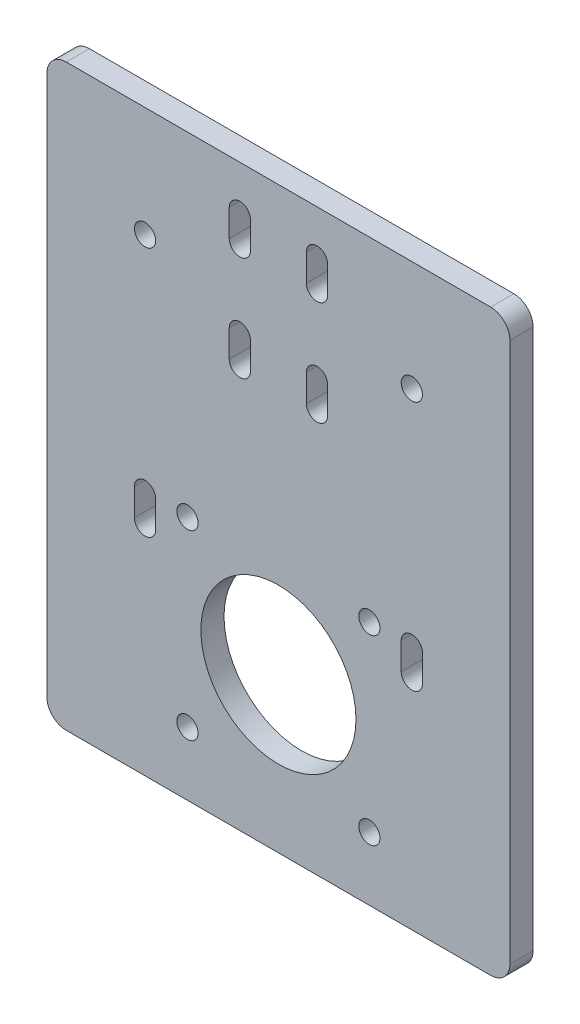
SolidWorks part; units mm, degrees
ref_plane "Front Plane" through (0, 0, 0) normal (0, 0, 1) x (1, 0, 0)
ref_plane "Top Plane" through (0, 0, 0) normal (0, 1, 0) x (1, 0, 0)
ref_plane "Right Plane" through (0, 0, 0) normal (1, 0, 0) x (0, 0, -1)
sketch "Sketch3" plane through (0, 0, 0) normal (0, 0, 1) x (1, 0, 0)
  line L1 (-55, -75) -> (55, -75)
  line L2 (-60, -70) -> (-60, 70)
  line L3 (-55, 75) -> (55, 75)
  line L4 (60, -70) -> (60, 70)
  line L5 (-60, -75) -> (60, 75) construction
  line L6 (-60, 75) -> (60, -75) construction
  arc A0 (-55, -75) -> (-60, -70) centre (-55, -70) cw
  arc A1 (55, -75) -> (60, -70) centre (55, -70) ccw
  arc A2 (55, 75) -> (60, 70) centre (55, 70) cw
  arc A3 (-60, 70) -> (-55, 75) centre (-55, 70) cw
  point P0 (0, 0)
  dimension "D3" = 5
  dimension "D1" = 120
  dimension "D2" = 150
extrude "Boss-Extrude1" add sketch "Sketch3" along normal blind 6
sketch "Sketch4" plane through (0, 0, 6) normal (0, 0, 1) x (1, 0, 0)
  line L0 (-55, -75) -> (55, -75) construction
  circle A0 centre (0, -35) radius 20.1
  dimension "D1" = 40.2
  dimension "D2" = 40
extrude "Cut-Extrude1" cut sketch "Sketch4" against normal blind 39.2
hole_wizard "M5 Clearance Hole1" positions "Sketch5" profile "Sketch6" hole size "M5" standard "ANSI Metric" end condition through all
sketch "Sketch5" plane through (0, 0, 6) normal (0, 0, 1) x (1, 0, 0)
  circle A0 centre (0, -35) radius 20.1 construction
  point P0 (-23.57, -11.43)
  point P2 (23.57, -11.43)
  point P4 (23.57, -58.57)
  point P6 (-23.57, -58.57)
  dimension "D2" = 23.57
  dimension "D3" = 23.57
  dimension "D5" = 23.57
  dimension "D1" = 47.14
  dimension "D4" = 23.57
sketch "Sketch6" plane through (-23.57, -11.43, 6) normal (1, 0, 0) x (0, -1, 0)
  line L0 (0, 0) -> (0, 6)
  line L1 (0, 6) -> (2.75, 6)
  line L2 (2.75, 6) -> (2.75, 0)
  line L5 (2.75, 0) -> (0, 0)
  line L11 (0, -6.35) -> (0, 107.95) construction
  dimension "Thru Hole Dia." = 5.5
  dimension "Thru Hole Depth" = 6
sketch "Sketch7" plane through (0, 0, 6) normal (0, 0, 1) x (1, 0, 0)
  line L0 (-34.57, -11.43) -> (-34.57, -18.43) construction
  line L1 (-31.82, -11.43) -> (-31.82, -18.43)
  line L2 (-37.32, -11.43) -> (-37.32, -18.43)
  line L3 (0, 37.3663) -> (0, -85.73) construction
  line L4 (34.57, -11.43) -> (34.57, -18.43) construction
  line L5 (31.82, -11.43) -> (31.82, -18.43)
  line L6 (37.32, -11.43) -> (37.32, -18.43)
  arc A0 (-31.82, -11.43) -> (-37.32, -11.43) centre (-34.57, -11.43) ccw
  arc A1 (-37.32, -18.43) -> (-31.82, -18.43) centre (-34.57, -18.43) ccw
  circle A2 centre (-23.57, -11.43) radius 2.75 construction
  arc A3 (31.82, -11.43) -> (37.32, -11.43) centre (34.57, -11.43) cw
  arc A4 (37.32, -18.43) -> (31.82, -18.43) centre (34.57, -18.43) cw
  point P2 (-34.57, -14.93)
  point P11 (34.57, -14.93)
  dimension "D1" = 2.75
  dimension "D2" = 7
  dimension "D3" = 11
extrude "Cut-Extrude2" cut sketch "Sketch7" against normal blind 6
hole_wizard "M5 Clearance Hole2" positions "Sketch8" profile "Sketch9" hole size "M5" standard "ANSI Metric" end condition through all
sketch "Sketch8" plane through (0, 0, 6) normal (0, 0, 1) x (1, 0, 0)
  point P0 (-34.57, 46.47)
  point P2 (34.57, 46.47)
  dimension "D1" = 61.4
sketch "Sketch9" plane through (-34.57, 46.47, 6) normal (1, 0, 0) x (0, -1, 0)
  line L0 (0, 0) -> (0, 6)
  line L1 (0, 6) -> (2.75, 6)
  line L2 (2.75, 6) -> (2.75, 0)
  line L5 (2.75, 0) -> (0, 0)
  line L11 (0, -6.35) -> (0, 107.95) construction
  dimension "Thru Hole Dia." = 5.5
  dimension "Thru Hole Depth" = 6
sketch "Sketch10" plane through (0, 0, 6) normal (0, 0, 1) x (1, 0, 0)
  line L0 (-10, 63.5) -> (-10, 56.5) construction
  line L1 (-7.25, 63.5) -> (-7.25, 56.5)
  line L2 (-12.75, 63.5) -> (-12.75, 56.5)
  line L3 (10, 63.5) -> (10, 56.5) construction
  line L4 (12.75, 63.5) -> (12.75, 56.5)
  line L5 (7.25, 63.5) -> (7.25, 56.5)
  line L6 (55, 75) -> (-55, 75) construction
  line L7 (34.57, 46.47) -> (-34.57, 46.47) construction
  line L8 (0, 37.3663) -> (0, -85.73) construction
  line L9 (-10, 29.44) -> (-10, 36.44) construction
  line L10 (-7.25, 29.44) -> (-7.25, 36.44)
  line L11 (-12.75, 29.44) -> (-12.75, 36.44)
  line L12 (10, 29.44) -> (10, 36.44) construction
  line L13 (12.75, 29.44) -> (12.75, 36.44)
  line L14 (7.25, 29.44) -> (7.25, 36.44)
  arc A0 (-7.25, 63.5) -> (-12.75, 63.5) centre (-10, 63.5) ccw
  arc A1 (-12.75, 56.5) -> (-7.25, 56.5) centre (-10, 56.5) ccw
  arc A2 (12.75, 63.5) -> (7.25, 63.5) centre (10, 63.5) ccw
  arc A3 (7.25, 56.5) -> (12.75, 56.5) centre (10, 56.5) ccw
  arc A4 (-7.25, 29.44) -> (-12.75, 29.44) centre (-10, 29.44) cw
  arc A5 (-12.75, 36.44) -> (-7.25, 36.44) centre (-10, 36.44) cw
  arc A6 (12.75, 29.44) -> (7.25, 29.44) centre (10, 29.44) cw
  arc A7 (7.25, 36.44) -> (12.75, 36.44) centre (10, 36.44) cw
  point P2 (-10, 60)
  point P7 (10, 60)
  point P28 (-10, 32.94)
  point P35 (10, 32.94)
  dimension "D1" = 2.75
  dimension "D2" = 7
  dimension "D3" = 15
  dimension "D4" = 20
  dimension "D5" = 10
extrude "Cut-Extrude3" cut sketch "Sketch10" against normal blind 6
sketch "Sketch11" plane through (0, 0, 0) normal (0, 0, -1) x (-1, 0, 0)
  line L0 (-41.0184, 46.47) -> (71.6367, 46.47) construction
